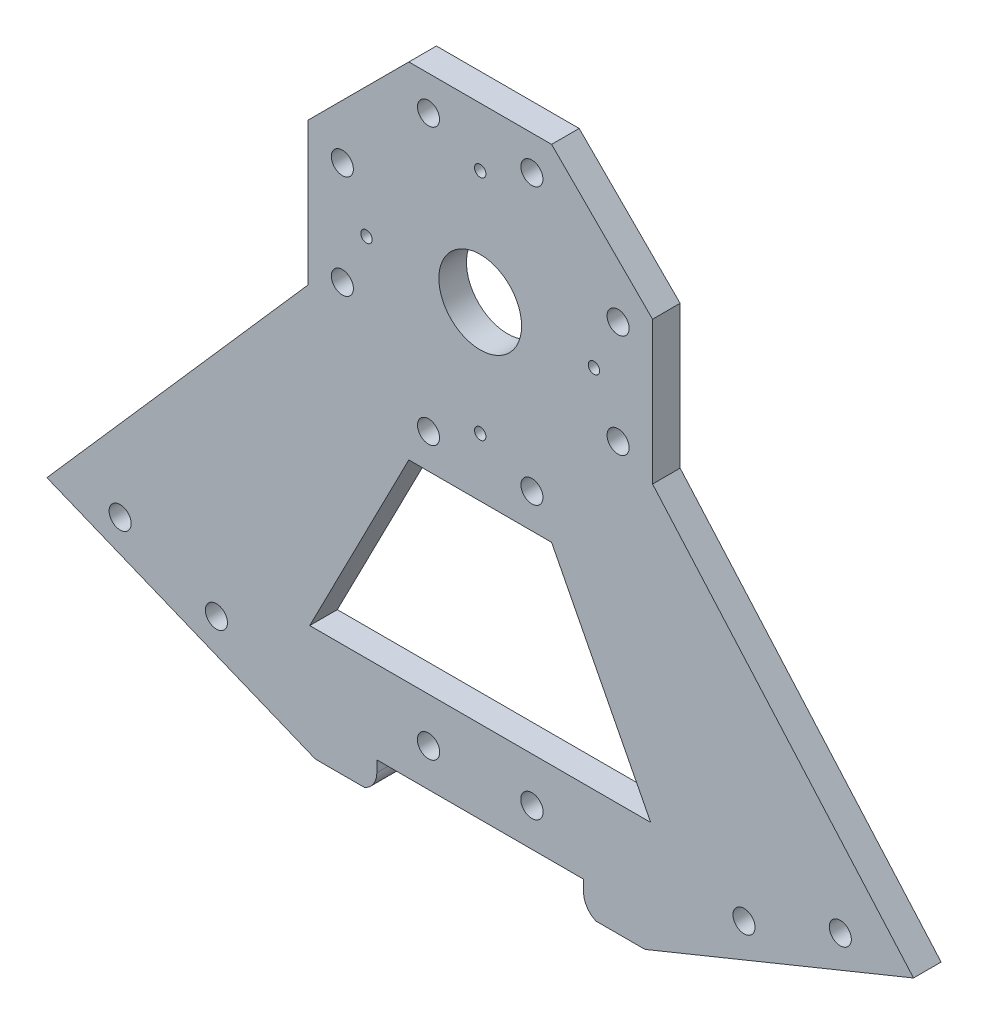
SolidWorks part; units mm, degrees
ref_plane "前视基准面" through (0, 0, 0) normal (0, 0, 1) x (1, 0, 0)
ref_plane "上视基准面" through (0, 0, 0) normal (0, 1, 0) x (1, 0, 0)
ref_plane "右视基准面" through (0, 0, 0) normal (1, 0, 0) x (0, 0, -1)
sketch "草图2" plane through (0, 0, 0) normal (0, 0, 1) x (1, 0, 0)
  line L1 (10.3553, 25) -> (-10.3553, 25)
  line L2 (-10.3553, 25) -> (-25, 10.3553)
  line L3 (-25, 10.3553) -> (-25, -10.3553)
  line L4 (-25, -10.3553) -> (-10.3553, -25)
  line L5 (-10.3553, -25) -> (10.3553, -25)
  line L6 (10.3553, -25) -> (25, -10.3553)
  line L7 (25, -10.3553) -> (25, 10.3553)
  line L8 (25, 10.3553) -> (10.3553, 25)
  circle A0 centre (0, 0) radius 25 construction
  circle A1 centre (-16.5, 0) radius 0.825
  circle A2 centre (0, 16.5) radius 0.825
  circle A3 centre (16.5, 0) radius 0.825
  circle A4 centre (0, -16.5) radius 0.825
  circle A5 centre (0, 0) radius 6
  point P22 (0, 0)
  dimension "D2" = 4
  dimension "D3" = 1.65
  dimension "D4" = 33
  dimension "D5" = 12
  dimension "D1" = 50
extrude "凸台-拉伸1" add sketch "草图2" along normal mid plane 4
sketch "草图4" plane through (0, 0, -2) normal (0, 0, -1) x (-1, 0, 0)
  line L0 (0, 2.2) -> (0, -2.2) construction
  line L1 (10.3553, -25) -> (-10.3553, -25) construction
  circle A0 centre (-7.5, -20) radius 1.6
  circle A1 centre (7.5, -20) radius 1.6
  circle A4 centre (-20, 7.5) radius 1.6
  circle A5 centre (-20, -7.5) radius 1.6
  circle A6 centre (7.5, 20) radius 1.6
  circle A7 centre (-7.5, 20) radius 1.6
  circle A8 centre (20, -7.5) radius 1.6
  circle A9 centre (20, 7.5) radius 1.6
  point P23 (0, 0)
  dimension "D1" = 15
  dimension "D2" = 5
  dimension "D3" = 3.2
  dimension "D4" = 4
extrude "切除-拉伸1" cut sketch "草图4" against normal blind 15
sketch "草图5" plane through (0, 0, 0) normal (0, 0, 1) x (1, 0, 0)
  line L0 (-25, -10.3553) -> (-80, -73)
  line L1 (-25, -10.3553) -> (-10.3553, -25) construction
  line L2 (-25, -10.3553) -> (-11.1777, -24.1777)
  line L3 (-11.1777, -24.1777) -> (-60, -73)
  line L4 (-60, -73) -> (-80, -73)
  line L5 (-10.3553, -25) -> (10.3553, -25) construction
  line L6 (0, -2.2) -> (0, 2.2) construction
  line L7 (60, -73) -> (80, -73)
  line L8 (11.1777, -24.1777) -> (60, -73)
  line L9 (25, -10.3553) -> (11.1777, -24.1777)
  line L10 (25, -10.3553) -> (80, -73)
  dimension "D1" = 48
  dimension "D2" = 160
  dimension "D3" = 120
extrude "凸台-拉伸2" add sketch "草图5" against normal mid plane 4
sketch "草图6" plane through (0, 0, 0) normal (0, 0, 1) x (1, 0, 0)
  line L0 (-60, -73) -> (-35, -73)
  line L9 (-35, -73) -> (-10.3553, -25)
  line L10 (-60, -73) -> (-11.1777, -24.1777)
  line L11 (-11.1777, -24.1777) -> (-10.3553, -25)
  line L12 (0, -2.2) -> (0, 2.2) construction
  line L13 (60, -73) -> (11.1777, -24.1777)
  line L14 (35, -73) -> (10.3553, -25)
  line L15 (60, -73) -> (35, -73)
  line L16 (11.1777, -24.1777) -> (10.3553, -25)
  dimension "D1" = 25
extrude "凸台-拉伸3" add sketch "草图6" along normal mid plane 4
sketch "草图21" plane through (0, 0, 2) normal (0, 0, 1) x (1, 0, 0)
  line L0 (-80, -73) -> (-35, -73) construction
  line L1 (-47.0875, -73) -> (47.0875, -73)
  line L2 (-47.0875, -73) -> (-47.0875, -53)
  line L3 (-47.0875, -53) -> (47.0875, -53)
  line L4 (47.0875, -73) -> (47.0875, -53)
  line L5 (-47.0875, -73) -> (47.0875, -53) construction
  line L6 (-47.0875, -53) -> (47.0875, -73) construction
  point P0 (0, -63)
  dimension "D1" = 20
extrude "凸台-拉伸5" add sketch "草图21" against normal blind 4
sketch "草图22" plane through (0, 0, 2) normal (0, 0, 1) x (1, 0, 0)
  line L0 (-25, -10.3553) -> (-80, -73) construction
  line L1 (80, -73) -> (25, -10.3553) construction
  line L2 (-72.0983, -64) -> (-93.6023, -86.7718)
  line L3 (-93.6023, -86.7718) -> (107.1386, -85.6421)
  line L4 (107.1386, -85.6421) -> (72.0983, -64)
  spline S0 degree 2 poles (-72.0983, -64) (0, -76) (72.0983, -64) knots 0 0 0 1 1 1
  dimension "D1" = 64
  dimension "D2" = 70
extrude "切除-拉伸10" cut sketch "草图22" against normal mid plane 14
sketch "草图23" plane through (0, 0, 2) normal (0, 0, 1) x (1, 0, 0)
  line L0 (24.7314, -53) -> (-24.7314, -53) construction
  line L1 (-15, -73.4501) -> (15, -73.4501)
  line L2 (-15, -73.4501) -> (-15, -65)
  line L3 (-15, -65) -> (15, -65)
  line L4 (15, -73.4501) -> (15, -65)
  line L5 (-15, -73.4501) -> (15, -65) construction
  line L6 (-15, -65) -> (15, -73.4501) construction
  point P0 (0, -69.225)
  dimension "D1" = 30
  dimension "D2" = 12
extrude "切除-拉伸11" cut sketch "草图23" against normal mid plane 14
sketch "草图24" plane through (0, 0, 2) normal (0, 0, 1) x (1, 0, 0)
  circle A0 centre (0, 0) radius 71.3352
chamfer "倒角6" distance 14 distance2 60 2 edges at (-72.0983, -64, 0) (72.0983, -64, 0) first distance on face at (-48.5491, -37.1777, 0) first distance on face at (48.5491, -37.1777, 0)
sketch "草图25" plane through (0, 0, 2) normal (0, 0, 1) x (1, 0, 0)
  line L0 (0, -2.2) -> (0, 2.2) construction
  circle A0 centre (-52.2352, -53.1485) radius 1.6
  circle A1 centre (-38.2687, -58.6199) radius 1.6
  circle A2 centre (38.2687, -58.6199) radius 1.6
  circle A3 centre (52.2352, -53.1485) radius 1.6
  dimension "D1" = 15
  dimension "D2" = 3.2
  dimension "D3" = 3.2
extrude "切除-拉伸12" cut sketch "草图25" against normal mid plane 14
fillet "圆角3" radius 3 2 edges at (-15, -69.7403, 0) (15, -69.7403, 0)
sketch "草图26" plane through (0, 0, 0) normal (1, 0, 0) x (0, 0, -1)
  line L0 (-2, 71.3352) -> (-2, -71.3352) construction
  line L1 (2, -53.4794) -> (2, -69.3361) construction
  line L2 (-2, -69.3667) -> (-2.2637, -70.2109)
  line L3 (-2.2637, -70.2109) -> (2.5473, -70.189)
  line L4 (2.5473, -70.189) -> (2, -69.3667)
  spline S0 degree 2 poles (-2, -69.3667) (0, -69.6868) (2, -69.3667) knots 0 0 0 1 1 1
extrude "切除-拉伸13" cut sketch "草图26" against normal mid plane 64
sketch "草图27" plane through (0, 0, -2) normal (0, 0, -1) x (-1, 0, 0)
  line L0 (-15, -65) -> (15, -65) construction
  line L1 (0, 2.6461) -> (0, -2.6461) construction
  circle A0 centre (-7.5, -59.5) radius 1.6214
  circle A1 centre (7.5, -59.5) radius 1.6214
  dimension "D1" = 5.5
  dimension "D2" = 15
extrude "切除-拉伸14" cut sketch "草图27" against normal mid plane 64
